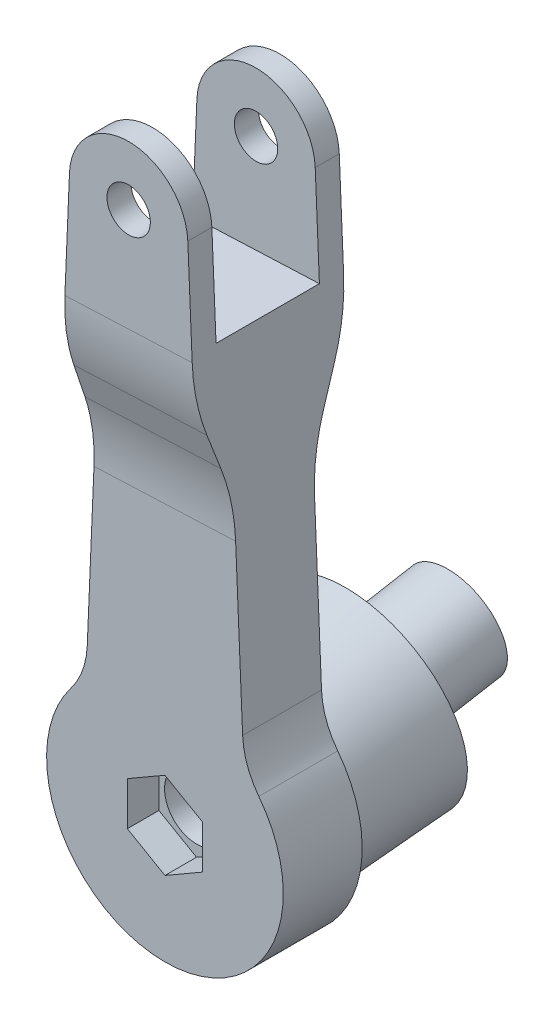
SolidWorks part; units mm, degrees
ref_plane "Front Plane" through (0, 0, 0) normal (0, 0, 1) x (1, 0, 0)
ref_plane "Top Plane" through (0, 0, 0) normal (0, 1, 0) x (1, 0, 0)
ref_plane "Right Plane" through (0, 0, 0) normal (1, 0, 0) x (0, 0, -1)
sketch "Sketch1" plane through (0, 0, 0) normal (0, 0, 1) x (1, 0, 0)
  line L0 (0, 0) -> (0, 69.866) construction
  line L1 (-7.5, 70.1838) -> (-10, 11.1803)
  line L3 (7.5, 70.1838) -> (10, 11.1803)
  arc A6 (-10, 11.1803) -> (10, 11.1803) centre (0, 0) ccw
  circle A7 centre (0, 69.866) radius 2.75
  arc A8 (-7.5, 70.1838) -> (7.5, 70.1838) centre (0, 69.866) cw
  dimension "D1" = 69.866
  dimension "D3" = 30
  dimension "D4" = 5.5
  dimension "D5" = 20
  dimension "D6" = 15
extrude "Boss-Extrude1" add sketch "Sketch1" along normal blind 19.2
sketch "Sketch13" plane through (10.4549, 0.443, 0) normal (0.9991, 0.0423, 0) x (0, 0, -1)
  line L0 (0, 77.3101) -> (-19.2, 77.3101) construction
  line L2 (-16.15, 77.3101) -> (-16.15, 57.3101)
  line L3 (-16.15, 57.3101) -> (-3.05, 57.3101)
  line L4 (-3.05, 77.3101) -> (-3.05, 57.3101)
  line L5 (-16.15, 77.3101) -> (-3.05, 57.3101) construction
  line L6 (-16.15, 57.3101) -> (-3.05, 77.3101) construction
  line L7 (-19.2, 77.3101) -> (-16.15, 77.3101) construction
  line L8 (-19.2, 10.747) -> (-19.2, 69.8034) construction
  line L9 (0, 10.747) -> (0, 69.8034) construction
  line L10 (-19.2, 52.3101) -> (-14.6, 39.6717)
  line L11 (-19.2, 10.747) -> (-19.2, 69.8034) construction
  line L12 (-14.6, 39.6717) -> (-14.6, -15)
  line L13 (-19.2, -15) -> (0, -15) construction
  line L14 (-19.2, 52.3101) -> (-19.2, 77.3101)
  line L15 (-19.2, 77.3101) -> (-16.15, 77.3101)
  line L16 (-9.6, 65.3081) -> (-9.6, -49934.6919) construction
  line L17 (0, 77.3101) -> (-3.05, 77.3101)
  line L18 (0, 52.3101) -> (0, 77.3101)
  line L19 (0, 52.3101) -> (-4.6, 39.6717)
  line L20 (-4.6, 39.6717) -> (-4.6, -15)
  line L21 (-3.05, 77.3101) -> (0, 77.3101) construction
  line L22 (-14.6, -15) -> (-4.6, -15)
  point P4 (-9.6, 67.3101)
  dimension "D1" = 3.05
  dimension "D2" = 20
  dimension "D3" = 160
  dimension "D4" = 5
  dimension "D5" = 10
extrude "Cut-Extrude4" cut sketch "Sketch13" against normal through all both and the other way through all flip side to cut
sketch "Sketch3" plane through (0, 0, 14.6) normal (0, 0, 1) x (1, 0, 0)
  line L1 (0, 5.5) -> (-4.7631, 2.75)
  line L2 (-4.7631, 2.75) -> (-4.7631, -2.75)
  line L3 (-4.7631, -2.75) -> (0, -5.5)
  line L4 (0, -5.5) -> (4.7631, -2.75)
  line L5 (4.7631, -2.75) -> (4.7631, 2.75)
  line L6 (4.7631, 2.75) -> (0, 5.5)
  circle A0 centre (0, 0) radius 4.7631 construction
  dimension "D1" = 9.5263
extrude "Cut-Extrude2" cut sketch "Sketch3" against normal blind 4
sketch "Sketch5" plane through (0, 0, 0) normal (1, 0, 0) x (0, 0, -1)
  line L0 (-5, 0) -> (10.4, 2.7154) construction
  line L1 (0, 52.7062) -> (0, 70.1838) construction
  line L2 (-4.6, 40.0791) -> (-4.6, 11.1803) construction
  line L3 (0, 52.7062) -> (0, 70.1838) construction
  point P13 (10.4, 2.7154)
  dimension "D1" = 10
  dimension "D2" = 5
  dimension "D3" = 15
ref_plane "Plane3" through (0, 2.7154, -10.4) normal (0, 0.1736, -0.9848) x (-1, 0, 0)
sketch "Sketch9" plane through (0, 2.7154, -10.4) normal (0, 0.1736, -0.9848) x (-1, 0, 0)
  circle A0 centre (0, -0.8682) radius 13
  circle A2 centre (0, -0.8682) radius 11 construction
  dimension "D1" = 22
  dimension "D2" = 2
sketch "Sketch4" plane through (0, 0, 10.6) normal (0, 0, 1) x (1, 0, 0)
  circle A0 centre (0, 0) radius 4.05
  dimension "D1" = 8.1
extrude "Cut-Extrude3" cut sketch "Sketch4" against normal blind 20
fillet "Fillet4" radius 10 2 edges at (-10, 11.1803, 9.6) (10, 11.1803, 9.6)
extrude "Boss-Extrude2" add sketch "Sketch9" against normal up to surface (13.0922 mm away) up to face at (0, 4.05, 4.6)
sketch "Sketch10" plane through (0, 1.8604, -10.5508) normal (0, 0.1736, -0.9848) x (-1, 0, 0)
  circle A0 centre (0, 0) radius 6.35
  dimension "D1" = 12.7
extrude "Boss-Extrude3" add sketch "Sketch10" along normal blind 12
draft "Draft1" type of draft neutral plane draft angle 3 faces to draft 1 face at (0, 12.3894, 4.6) neutral plane through (0, 1.8604, -10.5508) neutral plane normal (0, 0.1736, -0.9848) reverse direction yes parameters "D1"=3
fillet "Fillet5" radius 25 4 edges at (-0.0148, 52.3564, 0) (-0.0158, 39.7066, 4.6) (-0.0158, 39.7066, 14.6) (-0.0148, 52.3564, 19.2)
equation "\"Leg_Tilt\"=10"
equation "\"D1@Sketch5\"=\"Leg_Tilt\""
